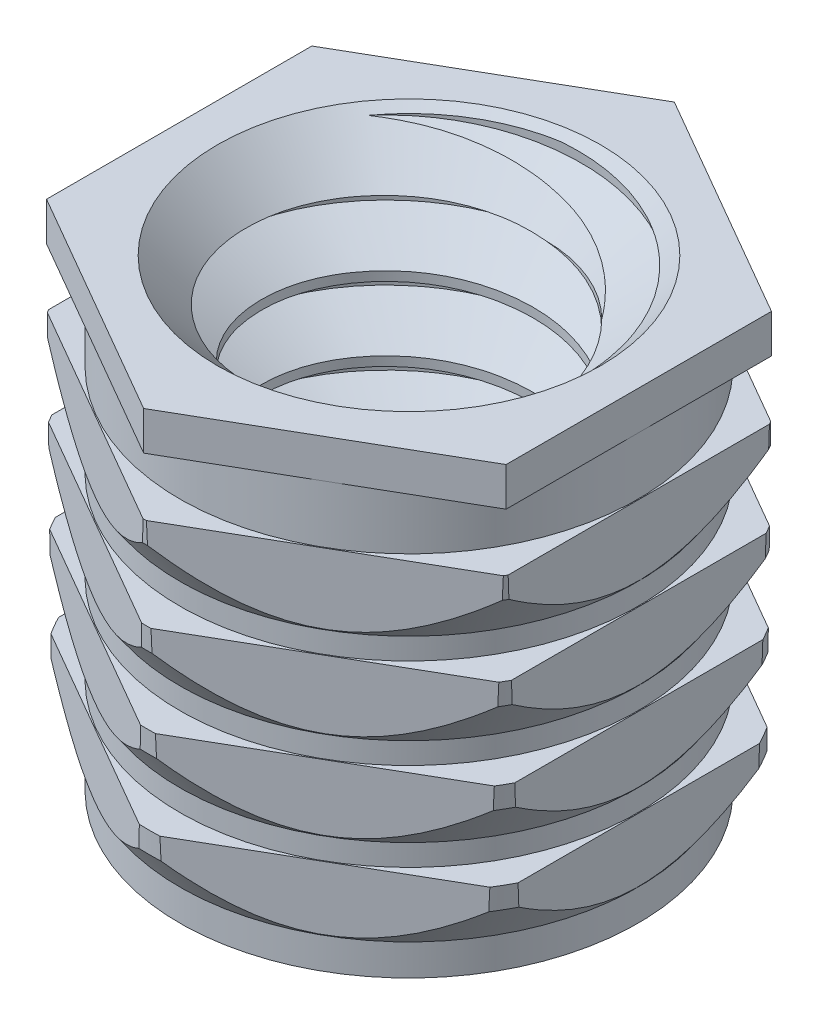
SolidWorks part; units mm, degrees
ref_plane "Front Plane" through (0, 0, 0) normal (0, 0, 1) x (1, 0, 0)
ref_plane "Top Plane" through (0, 0, 0) normal (0, 1, 0) x (1, 0, 0)
ref_plane "Right Plane" through (0, 0, 0) normal (1, 0, 0) x (0, 0, -1)
sketch "Sketch1" plane through (0, 0, 0) normal (0, 1, 0) x (1, 0, 0)
  line L0 (-3.9497, 0) -> (3.9497, 0) construction
  line L1 (-3.9497, 0) -> (-3.9624, 0) construction
  line L2 (0, 4.5754) -> (-3.9624, 2.2877)
  line L3 (-3.9624, 2.2877) -> (-3.9624, -2.2877)
  line L4 (-3.9624, -2.2877) -> (0, -4.5754)
  line L5 (0, -4.5754) -> (3.9624, -2.2877)
  line L6 (3.9624, -2.2877) -> (3.9624, 2.2877)
  line L7 (3.9624, 2.2877) -> (0, 4.5754)
  line L8 (3.9497, 0) -> (3.9624, 0) construction
  line L9 (-4.5754, 0) -> (-3.9624, 0) construction
  circle A0 centre (0, 0) radius 3.9497 construction
  circle A1 centre (0, 0) radius 3.9624 construction
  circle A2 centre (0, 0) radius 4.5754 construction
  dimension "OD" = 7.8994
  dimension "Hex" = 7.9248
extrude "Extrude1" add sketch "Sketch1" against normal blind 8.001
sketch "Sketch2" plane through (0, 0, 0) normal (0, 1, 0) x (1, 0, 0)
  circle A2 centre (0, 0) radius 3.175
  point P0 (-3.175, 0)
  dimension "Internal Thread OD" = 6.35
curve "Helix/Spiral1" pitch 1.27 height 22.9387 radius 3.175 centre (0, 0, 0) axis (0, -1, 0) start towards (0, 0, 1) parameters "Internal Thread Height"=22.9387, "Internal Thread Pitch"=1.27
sketch "Sketch3" plane through (0, 0, 0) normal (0, 0, 1) x (1, 0, 0)
  line L0 (-2.2126, 0.7144) -> (-2.2126, -0.5556) construction
  line L1 (-2.2126, -0.5556) -> (-3.3125, 0.0794) construction
  line L2 (-3.3125, 0.0794) -> (-2.2126, 0.7144) construction
  line L3 (-2.2126, 0.0794) -> (-2.3501, 0.0794) construction
  line L4 (-2.3501, 0.0794) -> (-3.175, 0.0794) construction
  line L5 (-3.175, 0.0794) -> (-3.3125, 0.0794) construction
  line L6 (-3.175, 0.1587) -> (-3.175, 0)
  line L7 (-2.3501, -0.4763) -> (-2.3501, 0.635) construction
  line L11 (-3.175, 0) -> (-2.2814, -0.5159)
  line L12 (-2.2814, -0.5159) -> (-2.2814, 0.6747)
  line L13 (-2.2814, 0.6747) -> (-3.175, 0.1587)
  point P18 (-2.2814, 0.0794)
  dimension "D1" = 1.27
  dimension "D2" = 0.1588
sketch "Sketch4" plane through (0, 0, 0) normal (0, 1, 0) x (-1, 0, 0)
  circle A0 centre (0, 0) radius 2.3501
extrude "Extrude2" cut sketch "Sketch4" against normal through all
chamfer "Chamfer1" distance 0.9525 angle 45 2 edges at (0, 0, 2.3501) (0, -8.001, 2.3501)
sketch "Sketch5" plane through (0, 0, 0) normal (0, 0, 1) x (1, 0, 0)
  line L0 (4.5754, 0) -> (-4.5754, 0) construction
  line L1 (-3.9497, 0) -> (-3.9497, -8.001) construction
  line L2 (-3.9497, 0) -> (-4.5754, 0) construction
  line L3 (0, 0) -> (0, -8.001) construction
  line L4 (-3.9624, -8.001) -> (0, -8.001) construction
  line L5 (-3.9497, -8.001) -> (-4.5754, -8.001)
  line L6 (-4.5754, 0) -> (-3.9624, 0) construction
  line L7 (-4.5754, 0) -> (-4.5754, -8.001) construction
  line L8 (-4.5754, -0.6667) -> (-4.4474, -8.001) construction
  line L9 (-4.5754, -0.6667) -> (-3.9497, -0.6668)
  line L10 (-4.5754, 0) -> (-4.5754, -0.6667)
  line L11 (-3.9497, -0.6668) -> (-3.9497, -1.6669)
  line L12 (-4.4963, -5.1978) -> (-3.9497, -5.9784)
  line L13 (-3.9497, -8.001) -> (-3.9497, -7.4619)
  line L14 (-3.9497, -5.9784) -> (-3.9497, -6.3488)
  line L15 (-3.9497, -1.6669) -> (-4.5579, -1.6669)
  line L16 (-4.5579, -1.6669) -> (-4.5515, -2.0372)
  line L17 (-4.5515, -2.0372) -> (-3.9497, -2.8967)
  line L18 (-3.9497, -6.3488) -> (-4.4762, -6.3488)
  line L19 (-4.5754, 0) -> (-5.2011, 0)
  line L20 (-5.2011, 0) -> (-5.2011, -8.001)
  line L21 (-5.2011, -8.001) -> (-4.5754, -8.001)
  line L22 (-3.9497, -3.2671) -> (-4.53, -3.2671)
  line L23 (-3.9497, -2.8967) -> (-3.9497, -3.2671)
  line L24 (-4.53, -3.2671) -> (-4.5235, -3.6374)
  line L25 (-4.5235, -3.6374) -> (-3.9497, -4.457)
  line L26 (-3.9497, -4.8274) -> (-4.5028, -4.8274)
  line L27 (-4.5028, -4.8274) -> (-4.4963, -5.1978)
  line L28 (-4.4762, -6.3488) -> (-4.4697, -6.7192)
  line L29 (-3.9497, -4.457) -> (-3.9497, -4.8274)
  line L30 (-4.4697, -6.7192) -> (-3.9497, -7.4619)
  dimension "D1" = 0.6667
  dimension "D2" = 1
  dimension "D5" = 35
  dimension "D6" = 1.0001
  dimension "D3" = 1.6002
revolve "Cut-Revolve1" cut sketch "Sketch5" angle 360 about L3
sketch "Sketch6" plane through (0, 0, 0) normal (0, 1, 0) x (1, 0, 0)
  line L0 (0, 0) -> (2.3353, -2.3353) construction
  line L1 (0, 0) -> (0, -3.3026) construction
  circle A0 centre (0, 0) radius 3.3026 construction
  point P8 (2.3353, -2.3353)
  dimension "D1" = 45
sweep "Cut-Sweep1" cut profiles "Sketch3" path "Helix/Spiral1"
ref_plane "Contact Plane 1" through (0, 0, 0) normal (0, 1, 0) x (1, 0, 0)
ref_plane "Contact Plane 2" through (0, -8.001, 0) normal (0, -1, 0) x (-1, 0, 0)
ref_axis "Center Axis 1" through (0, -7.0485, 0) along (0, 1, 0)
equation "\"Internal Thread Height@Helix/Spiral1\" = \"Internal Thread Pitch@Helix/Spiral1\" + \"Length@Extrude1\" + 0.5381"
equation "\"D1@Sketch3\" = \"Internal Thread Pitch@Helix/Spiral1\""
equation "\"D2@Sketch3\" = \"D1@Sketch3\" * 1 / 8"
equation "\"D1@Chamfer1\" = \"Internal Thread Pitch@Helix/Spiral1\" * 6 / 8"
equation "\"D1@Sketch5\" = \"Length@Extrude1\"  * 1 / 12"
equation "\"D6@Sketch5\" = \"D1@Sketch5\" * 1.5"
equation "\"D3@Sketch5\" = \"Length@Extrude1\"  * 1 / 5"
